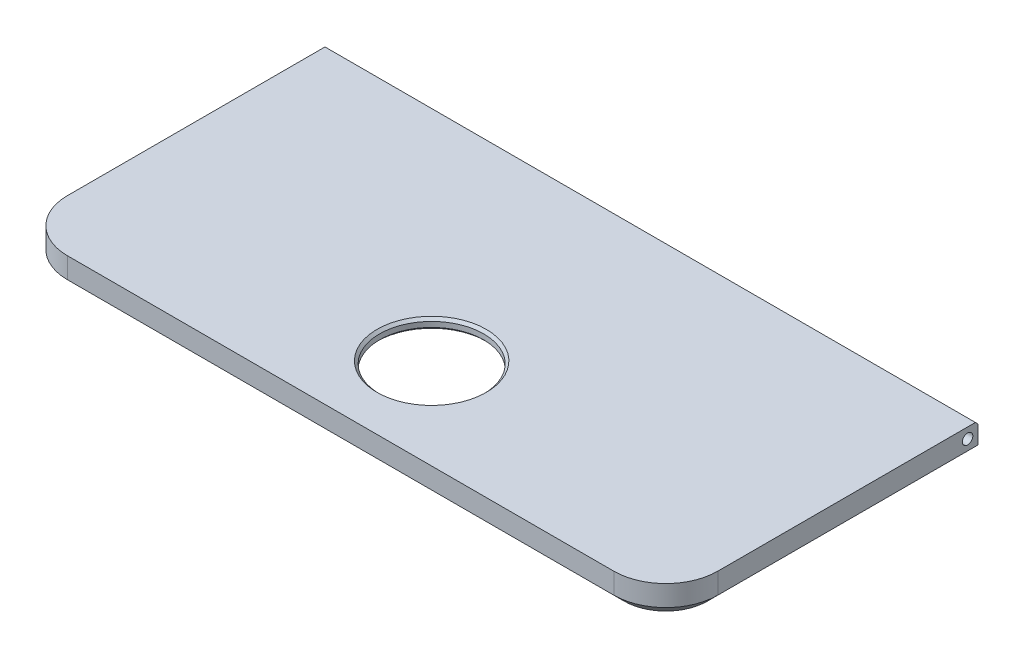
SolidWorks part; units mm, degrees
material "ПК/АБС"
ref_plane "Спереди" through (0, 0, 0) normal (0, 0, 1) x (1, 0, 0)
ref_plane "Сверху" through (0, 0, 0) normal (0, 1, 0) x (1, 0, 0)
ref_plane "Справа" through (0, 0, 0) normal (1, 0, 0) x (0, 0, -1)
sketch "Эскиз1" plane through (0, 0, 0) normal (0, 1, 0) x (1, 0, 0)
  line L1 (-62.5, -30) -> (62.5, -30)
  line L2 (-62.5, -30) -> (-62.5, 30)
  line L3 (-62.5, 30) -> (62.5, 30)
  line L4 (62.5, -30) -> (62.5, 30)
  line L5 (-62.5, -30) -> (62.5, 30) construction
  line L6 (-62.5, 30) -> (62.5, -30) construction
  point P0 (0, 0)
  dimension "D1" = 125
  dimension "D2" = 60
extrude "Бобышка-Вытянуть1" add sketch "Эскиз1" along normal blind 6
fillet "Скругление1" radius 10 2 edges at (-62.5, 3, 30) (62.5, 3, 30)
sketch "Эскиз2" plane through (0, 0, 0) normal (0, -1, 0) x (1, 0, 0)
  line L8 (-59, 20) -> (-59, -26.5)
  line L9 (-59, -26.5) -> (59, -26.5)
  line L10 (59, -26.5) -> (59, 20)
  line L11 (52.5, 26.5) -> (-52.5, 26.5)
  line L12 (-59, 20) -> (-59, -26.5)
  line L13 (-59, -26.5) -> (59, -26.5)
  line L14 (59, -26.5) -> (59, 20)
  line L15 (52.5, 26.5) -> (-52.5, 26.5)
  arc A4 (59, 20) -> (52.5, 26.5) centre (52.5, 20) ccw
  arc A5 (-52.5, 26.5) -> (-59, 20) centre (-52.5, 20) ccw
  arc A6 (59, 20) -> (52.5, 26.5) centre (52.5, 20) ccw
  arc A7 (-52.5, 26.5) -> (-59, 20) centre (-52.5, 20) ccw
  dimension "D1" = 3.5
extrude "Вырез-Вытянуть1" cut sketch "Эскиз2" against normal blind 4
chamfer "Фаска1" distance 2 angle 45 6 edges at (0, 0, -30) (-62.5, 0, -5) (62.5, 0, -5) (-59.5711, 0, 27.0711) (59.5711, 0, 27.0711) (0, 0, 30)
sketch "Эскиз4" plane through (0, 4, 0) normal (0, -1, 0) x (1, 0, 0)
  line L6 (-59, -26.5) -> (59, -26.5)
  line L7 (-59, -26.5) -> (-59, -25)
  line L8 (-59, -25) -> (59, -25)
  line L9 (59, -26.5) -> (59, -25)
  line L14 (62.5, -30) -> (-62.5, -30) construction
  point P5 (64, -31.5)
  dimension "D2" = 5
extrude "Бобышка-Вытянуть3" add sketch "Эскиз4" along normal up to surface (4 mm away) up to face at (0, 0, 7.219)
sketch "Эскиз3" plane through (62.5, 0, 0) normal (1, 0, 0) x (0, 0, -1)
  line L0 (-20, 6) -> (30, 6) construction
  line L1 (30, 6) -> (30, 2) construction
  circle A0 centre (28, 4) radius 1
  dimension "D2" = 2
  dimension "D1" = 2
  dimension "D3" = 2
extrude "Вырез-Вытянуть2" cut sketch "Эскиз3" against normal blind 10
sketch "Эскиз5" plane through (-62.5, 0, 0) normal (-1, 0, 0) x (0, 0, 1)
  line L0 (-30, 6) -> (-30, 2) construction
  line L1 (-30, 6) -> (20, 6) construction
  circle A0 centre (-28, 4) radius 1
  dimension "D3" = 2
  dimension "D1" = 2
  dimension "D2" = 2
extrude "Вырез-Вытянуть3" cut sketch "Эскиз5" against normal blind 10
sketch "Эскиз6" plane through (0, 4, 0) normal (0, -1, 0) x (1, 0, 0)
  line L0 (0, 30) -> (0, 12.5) construction
  line L1 (-52.5, 30) -> (52.5, 30) construction
  circle A0 centre (0, 12.5) radius 10
  dimension "D2" = 20
  dimension "D1" = 17.5
extrude "Вырез-Вытянуть4" cut sketch "Эскиз6" against normal up to surface (2 mm away) up to face at (0, 6, 7.357)
chamfer "Фаска2" distance 0.5 angle 45 3 edges at (0, 6, -30) (0, 4, 2.5) (0, 6, 2.5)
